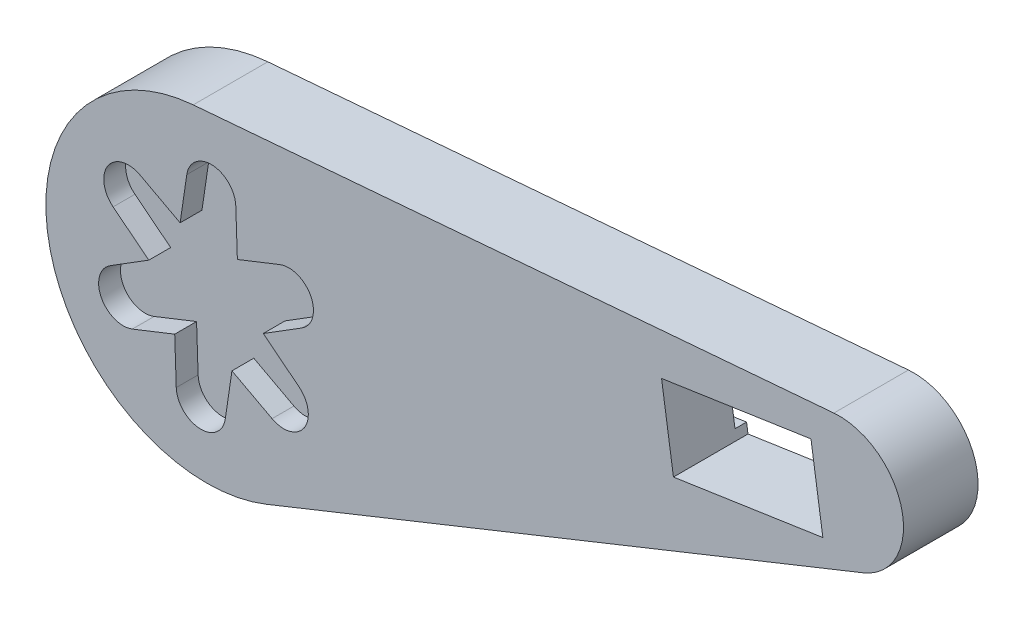
SolidWorks part; units mm, degrees
ref_plane "前视基准面" through (0, 0, 0) normal (0, 0, 1) x (1, 0, 0)
ref_plane "上视基准面" through (0, 0, 0) normal (0, 1, 0) x (1, 0, 0)
ref_plane "右视基准面" through (0, 0, 0) normal (1, 0, 0) x (0, 0, -1)
other "Configuration Table"
sketch "草图1" plane through (0, 0, 0) normal (0, 0, 1) x (1, 0, 0)
  line L0 (0, 0) -> (99.6542, 8.309)
  line L1 (11.3727, -48.1212) -> (104.2033, -10.9395)
  line L4 (6.8649, -17.3962) -> (6.6237, -10.3291)
  line L5 (10.8954, -25.35) -> (16.8951, -21.6076)
  line L7 (-2.0386, -16.9098) -> (-1.0032, -9.8995)
  line L8 (6.8649, -17.3962) -> (13.4537, -14.7877)
  line L9 (6.0225, -32.8175) -> (12.2633, -36.1422)
  line L10 (10.8954, -25.35) -> (16.4488, -29.7518)
  line L11 (-2.881, -32.3311) -> (-2.6398, -39.3982)
  line L12 (6.0225, -32.8175) -> (4.9871, -39.8277)
  line L13 (-6.9115, -24.3773) -> (-12.9112, -28.1197)
  line L14 (-2.881, -32.3311) -> (-9.4698, -34.9395)
  line L15 (-2.0386, -16.9098) -> (-8.2794, -13.5851)
  line L16 (-6.9115, -24.3773) -> (-12.4649, -19.9754)
  arc A0 (11.3727, -48.1212) -> (0, 0) centre (2.0773, -24.9136) cw
  arc A2 (99.6542, 8.309) -> (104.2033, -10.9395) centre (100.4851, -1.6564) cw
  arc A4 (6.6237, -10.3291) -> (-1.0032, -9.8995) centre (2.7908, -10.4599) ccw
  arc A5 (16.8951, -21.6076) -> (13.4537, -14.7877) centre (14.8654, -18.3536) ccw
  arc A6 (12.2633, -36.1422) -> (16.4488, -29.7518) centre (14.0665, -32.7574) ccw
  arc A7 (-2.6398, -39.3982) -> (4.9871, -39.8277) centre (1.1931, -39.2674) ccw
  arc A8 (-12.9112, -28.1197) -> (-9.4698, -34.9395) centre (-10.8815, -31.3737) ccw
  arc A9 (-8.2794, -13.5851) -> (-12.4649, -19.9754) centre (-10.0826, -16.9699) ccw
  point P6 (6.9282, 0.5777)
  point P8 (2.0773, -24.9136)
  point P9 (100.4851, -1.6564)
  point P12 (108.3067, 6.9355)
  point P14 (-78.4232, -44.2943)
  point P15 (6.626, -10.3962)
  point P16 (6.626, -10.3962)
  point P19 (0, 0)
  point P20 (0, 0)
  point P21 (0, 0)
  point P47 (1.992, -24.8636)
  dimension "D2" = 9
  dimension "D3" = 7
  dimension "D1" = 100
  dimension "D4" = 6
extrude "凸台-拉伸5" add sketch "草图1" along normal blind 15 contours L1 A2 L0 A0
sketch "草图9" plane through (0, 0, 0) normal (0, 0, -1) x (-1, 0, 0)
  line L0 (-96.0925, 3.0452) -> (-72.8508, -0.4291)
  line L1 (-72.8508, -0.4291) -> (-74.6988, -12.7918)
  line L2 (-74.6988, -12.7918) -> (-97.9406, -9.3175)
  line L3 (-97.9406, -9.3175) -> (-96.0925, 3.0452)
  line L4 (-73.0304, -1.6311) -> (-68.0854, -2.3703)
  line L5 (-74.4743, -11.2901) -> (-69.5293, -12.0293)
  line L6 (-68.0854, -2.3703) -> (-69.5293, -12.0293)
  point P2 (-73.7748, -6.6105)
  point P5 (-73.0304, -1.6311)
  point P6 (-74.4743, -11.2901)
  dimension "D1" = 23.5
extrude "切除-拉伸8" cut sketch "草图9" against normal blind 5.2 contours L6 L4 L1 L5 region at (71.2799, -6.8302, 0)
extrude "切除-拉伸9" cut sketch "草图9<5>" against normal blind 15 contours L3 L0 L1 L2
sketch "草图9<5>" plane through (0, 0, 0) normal (0, 0, -1) x (-1, 0, 0) same geometry as "草图9"
sketch "草图12" plane through (0, 0, 15) normal (0, 0, 1) x (1, 0, 0)
  line L0 (74.6988, -12.7918) -> (97.9406, -9.3175) construction
  line L2 (72.7858, -6.7583) -> (72.7823, -6.7588)
  circle A0 centre (72.2919, -6.8321) radius 0.4958
  circle A1 centre (98.4995, -2.9145) radius 0.4958
  point P0 (73.7748, -6.6105)
  point P1 (86.3197, -11.0546)
curve "曲线1"
sketch "草图1<10>" plane through (0, 0, 0) normal (0, 0, 1) x (1, 0, 0) same geometry as "草图1"
ref_plane "基准面2" through (6.6237, -10.3291, 15) normal (-0.0341, 0.9994, 0) x (0.9994, 0.0341, 0)
sketch "草图16" plane through (0, 0, 0) normal (0, 0, -1) x (-1, 0, 0)
extrude "切除-拉伸10" cut sketch "草图1<11>" along normal blind 3.4
sketch "草图1<11>" plane through (0, 0, 0) normal (0, 0, 1) x (1, 0, 0) same geometry as "草图1"
ref_plane "基准面3" through (16.8951, -21.6076, 15) normal (0.8485, 0.5292, 0) x (0, 0, -1)
sketch "草图25" plane through (0, 0, 15) normal (0, 0, 1) x (1, 0, 0)
  line L0 (-2.0386, -16.9098) -> (-8.2794, -13.5851) construction
  line L1 (-2.0386, -16.9098) -> (-8.2794, -13.5851)
  line L2 (11.3727, -48.1212) -> (104.2033, -10.9395)
  line L3 (99.6542, 8.309) -> (0, 0)
  line L4 (11.3727, -48.1212) -> (104.2033, -10.9395)
  line L5 (99.6542, 8.309) -> (0, 0)
  line L6 (-6.9115, -24.3773) -> (-12.9112, -28.1197) construction
  line L7 (-2.881, -32.3311) -> (-9.4698, -34.9395) construction
  line L8 (-2.881, -32.3311) -> (-2.6398, -39.3982) construction
  line L9 (6.0225, -32.8175) -> (4.9871, -39.8277) construction
  line L10 (6.0225, -32.8175) -> (12.2633, -36.1422) construction
  line L11 (10.8954, -25.35) -> (16.4488, -29.7518) construction
  line L12 (10.8954, -25.35) -> (16.8951, -21.6076) construction
  line L13 (6.8649, -17.3962) -> (13.4537, -14.7877) construction
  line L14 (6.8649, -17.3962) -> (6.6237, -10.3291) construction
  line L15 (-2.0386, -16.9098) -> (-1.0032, -9.8995) construction
  line L16 (-6.9115, -24.3773) -> (-12.4649, -19.9754) construction
  line L17 (-6.9115, -24.3773) -> (-12.9112, -28.1197)
  line L18 (-2.881, -32.3311) -> (-9.4698, -34.9395)
  line L19 (-2.881, -32.3311) -> (-2.6398, -39.3982)
  line L20 (6.0225, -32.8175) -> (4.9871, -39.8277)
  line L21 (6.0225, -32.8175) -> (12.2633, -36.1422)
  line L22 (10.8954, -25.35) -> (16.4488, -29.7518)
  line L23 (10.8954, -25.35) -> (16.8951, -21.6076)
  line L24 (6.8649, -17.3962) -> (13.4537, -14.7877)
  line L25 (6.8649, -17.3962) -> (6.6237, -10.3291)
  line L26 (-2.0386, -16.9098) -> (-1.0032, -9.8995)
  line L27 (-2.0386, -16.9098) -> (-8.2794, -13.5851)
  line L28 (-6.9115, -24.3773) -> (-12.4649, -19.9754)
  arc A0 (-12.9112, -28.1197) -> (-9.4698, -34.9395) centre (-10.8815, -31.3737) ccw construction
  arc A1 (-2.6398, -39.3982) -> (4.9871, -39.8277) centre (1.1931, -39.2674) ccw construction
  arc A2 (0, 0) -> (11.3727, -48.1212) centre (2.0773, -24.9136) ccw
  arc A3 (104.2033, -10.9395) -> (99.6542, 8.309) centre (100.4851, -1.6564) ccw
  arc A4 (0, 0) -> (11.3727, -48.1212) centre (2.0773, -24.9136) ccw
  arc A5 (104.2033, -10.9395) -> (99.6542, 8.309) centre (100.4851, -1.6564) ccw
  arc A6 (12.2633, -36.1422) -> (16.4488, -29.7518) centre (14.0665, -32.7574) ccw construction
  arc A7 (16.8951, -21.6076) -> (13.4537, -14.7877) centre (14.8654, -18.3536) ccw construction
  arc A8 (6.6237, -10.3291) -> (-1.0032, -9.8995) centre (2.7908, -10.4599) ccw construction
  arc A9 (-8.2794, -13.5851) -> (-12.4649, -19.9754) centre (-10.0826, -16.9699) ccw construction
  arc A10 (-12.9112, -28.1197) -> (-9.4698, -34.9395) centre (-10.8815, -31.3737) ccw
  arc A11 (-2.6398, -39.3982) -> (4.9871, -39.8277) centre (1.1931, -39.2674) ccw
  arc A12 (12.2633, -36.1422) -> (16.4488, -29.7518) centre (14.0665, -32.7574) ccw
  arc A13 (16.8951, -21.6076) -> (13.4537, -14.7877) centre (14.8654, -18.3536) ccw
  arc A14 (6.6237, -10.3291) -> (-1.0032, -9.8995) centre (2.7908, -10.4599) ccw
  arc A15 (-8.2794, -13.5851) -> (-12.4649, -19.9754) centre (-10.0826, -16.9699) ccw
  dimension "D1" = 0
extrude "切除-拉伸11" cut sketch "草图25" against normal blind 3.4 contours L1 A15 L28 L17 A10 L18 L19 A11 L20 L21 A12 L22 L23 A13 L24 L25 A14 L26 region at (1.992, -24.8636, 15)
